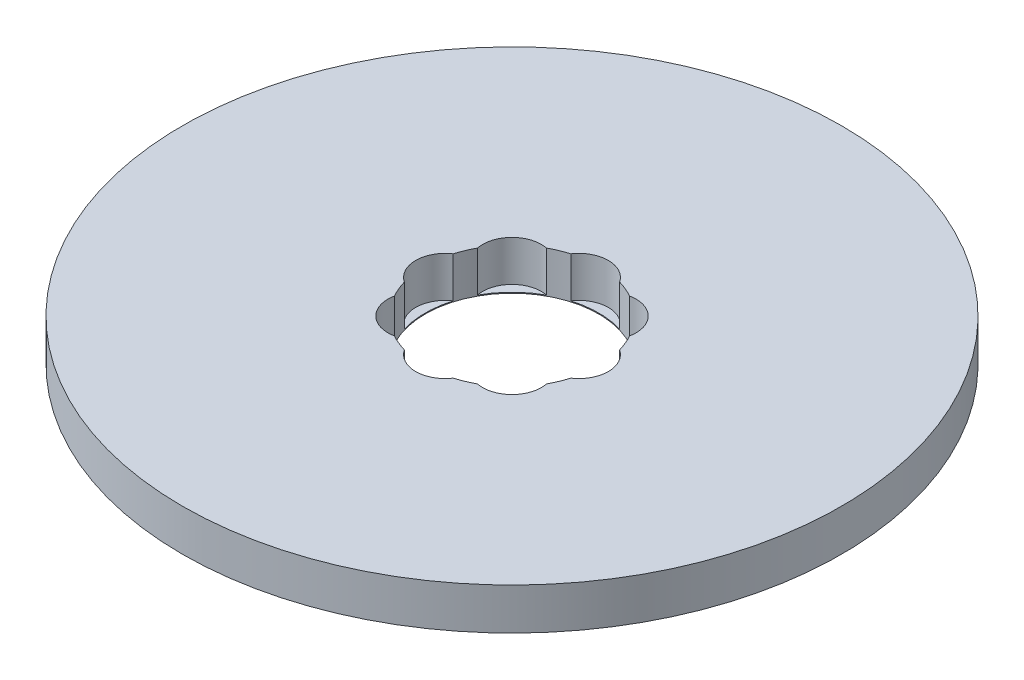
SolidWorks part; units mm, degrees
ref_plane "Front Plane" through (0, 0, 0) normal (0, 0, 1) x (1, 0, 0)
ref_plane "Top Plane" through (0, 0, 0) normal (0, 1, 0) x (1, 0, 0)
ref_plane "Right Plane" through (0, 0, 0) normal (1, 0, 0) x (0, 0, -1)
sketch "Sketch1" plane through (0, 0, 0) normal (0, 1, 0) x (1, 0, 0)
  circle A0 centre (0, 0) radius 95
  dimension "FLANGE_OD" = 190
extrude "Boss-Extrude1" add sketch "Sketch1" along normal blind 12
sketch "Sketch2" plane through (0, 0, 0) normal (0, 1, 0) x (1, 0, 0)
  circle A0 centre (0, 0) radius 25
  dimension "BORE_D" = 50
extrude "Cut-Extrude1" cut sketch "Sketch2" along normal through all
sketch "Sketch3" plane through (0, 12, 0) normal (0, 1, 0) x (1, 0, 0)
  circle A0 centre (0, 0) radius 19.3002 construction
  circle A1 centre (-19.3002, 0) radius 8.4575
  dimension "BOLT_D" = 16.9149
  dimension "BOLT_PCD" = 38.6004
extrude "Cut-Extrude2" cut sketch "Sketch3" against normal blind 11.7483
pattern_circular "CirPattern1" count 8 over 360 about axis through (0, 0, 0) along (0, 1, 0) of "Cut-Extrude2"
